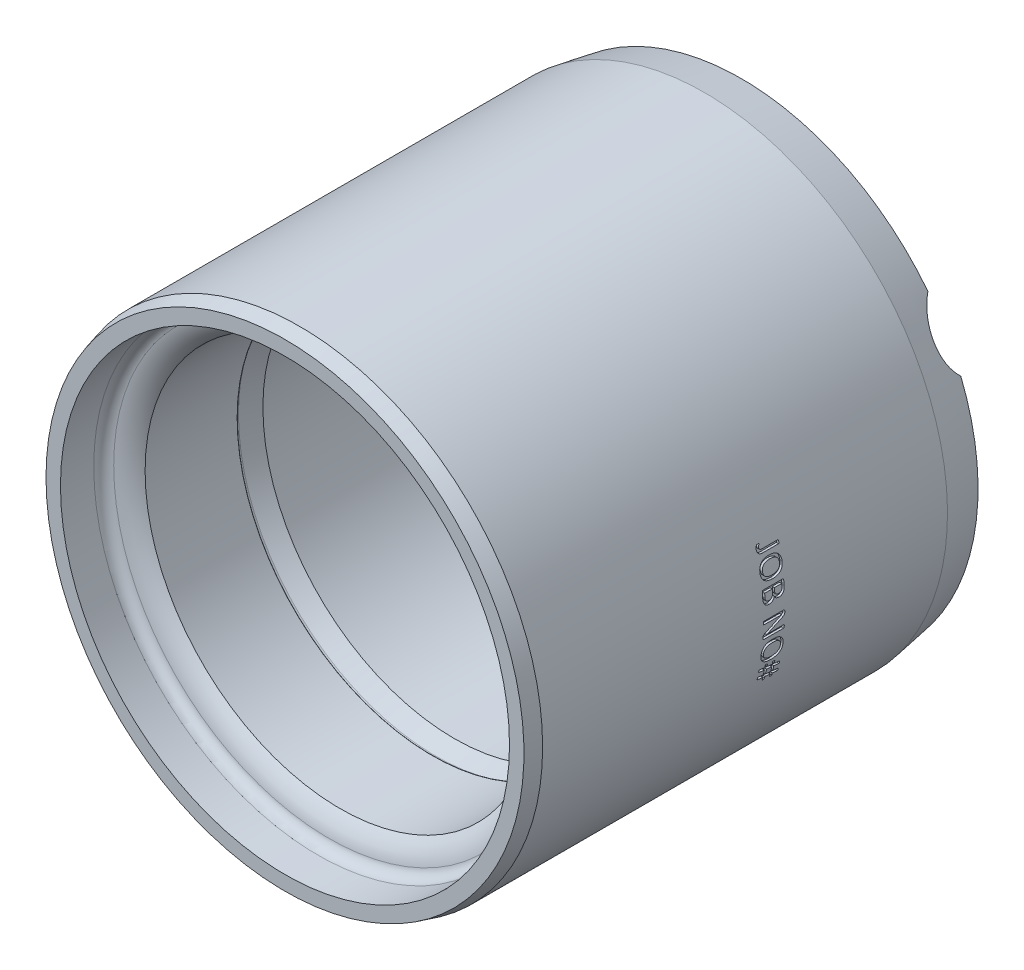
SolidWorks part; units mm, degrees
ref_plane "Front Plane" through (0, 0, 0) normal (0, 0, 1) x (1, 0, 0)
ref_plane "Top Plane" through (0, 0, 0) normal (0, 1, 0) x (1, 0, 0)
ref_plane "Right Plane" through (0, 0, 0) normal (1, 0, 0) x (0, 0, -1)
sketch "Sketch1" plane through (0, 0, 0) normal (1, 0, 0) x (0, 0, -1)
  line L0 (0, 0) -> (-62, 0) construction
  line L1 (0, 32.15) -> (0, 27)
  line L2 (-4.5, 22.75) -> (-2.6734, 22.75)
  line L10 (-5, 33) -> (-60, 33)
  line L13 (-60, 33) -> (-62, 32.4641)
  line L14 (-42, 26.5) -> (-54.5, 26.5)
  line L15 (-62, 30.5) -> (-62, 32.4641)
  line L16 (-57.4765, 30.5) -> (-62, 30.5)
  line L17 (-42, 26.4758) -> (-42, 26.5)
  line L18 (-39, 26) -> (-41.4693, 26.8539)
  line L19 (-7.5, 26) -> (-39, 26)
  line L21 (0, 27) -> (-0.7416, 24.2324)
  line L22 (-5, 23.25) -> (-5, 25.7)
  line L24 (-5, 33) -> (0, 32.15)
  line L25 (-5.8, 26.5) -> (-6.634, 26.5)
  line L26 (-6.634, 26.5) -> (-7.5, 26)
  arc A5 (-5, 23.25) -> (-4.5, 22.75) centre (-4.5, 23.25) ccw
  arc A6 (-54.5, 26.5) -> (-56, 29.2644) centre (-51.0783, 30.1458) cw
  arc A8 (-41.4693, 26.8539) -> (-42, 26.4758) centre (-41.6, 26.4758) ccw
  arc A9 (-0.7416, 24.2324) -> (-2.6734, 22.75) centre (-2.6734, 24.75) cw
  arc A11 (-56, 29.2644) -> (-57.4765, 30.5) centre (-57.4765, 29) ccw
  arc A12 (-5, 25.7) -> (-5.8, 26.5) centre (-5.8, 25.7) ccw
  point P14 (-42, 27.0374)
  point P19 (-1.1388, 22.75)
  dimension "D2" = 0.5
  dimension "D4" = 0.8
  dimension "D11" = 26
  dimension "D12" = 26.5
  dimension "D3" = 5
  dimension "D22" = 30
  dimension "D23" = 0.4
  dimension "D24" = 2
  dimension "D8" = 1.5
  dimension "D5" = 45.5
  dimension "D6" = 39
  dimension "D7" = 42
  dimension "D9" = 2
  dimension "D10" = 62
  dimension "D13" = 27.0374
  dimension "D14" = 54
  dimension "D15" = 61
  dimension "D16" = 33
  dimension "D17" = 15
  dimension "D18" = 5
  dimension "D19" = 53
  dimension "D20" = 9.648
  dimension "D21" = 5
  dimension "D25" = 6
  dimension "D26" = 7.5
  dimension "D27" = 15
  dimension "D28" = 2.5
revolve "Revolve1" add sketch "Sketch1" angle 360 about L0
sketch "Sketch9" plane through (0, 0, 0) normal (0, 1, 0) x (1, 0, 0)
  line L4 (-32.4641, -62) -> (32.4641, -62) construction
  line L5 (-4.4721, 0) -> (4.4721, 0)
  line L6 (33, 0) -> (-33, 0) construction
  arc A1 (-4.4721, 0) -> (4.4721, 0) centre (0, 4) ccw
  dimension "D3" = 60
  dimension "D1" = 6
extrude "Cut-Extrude3" cut sketch "Sketch9" against normal up to surface (32.6956 mm away) contours A1 L5 up to face at (-33, 0, 60)
pattern_circular "CirPattern3" count 3 over 360 about axis through (0, 0, 0) along (0, 0, -1) of "Cut-Extrude3" reverse direction yes
ref_plane "Plane1" through (40, 0, 0) normal (1, 0, 0) x (0, 0, -1)
sketch "Sketch10" plane through (40, 0, 0) normal (1, 0, 0) x (0, 0, -1)
  line L0 (-30.0113, 33) -> (-30.0113, -33) construction
  line L1 (-5, 33) -> (-60, 33) construction
  line L2 (-60, -33) -> (-5, -33) construction
  text T0 "JOB NO#" font "Calibri" height in points 11
extrude "Cut-Extrude4" cut sketch "Sketch10" against normal blind 11
ref_plane "Plane2" through (0, 0, 60) normal (0, 0, 1) x (1, 0, 0)
sketch "Sketch11" plane through (0, 0, 60) normal (0, 0, 1) x (1, 0, 0)
  circle A0 centre (0, 0) radius 32.7
  circle A1 centre (0, 0) radius 31.5
  circle A2 centre (0, 0) radius 33 construction
  dimension "D1" = 0.3
  dimension "D2" = 1.2
extrude "Boss-Extrude1" add sketch "Sketch11" against normal blind 45
